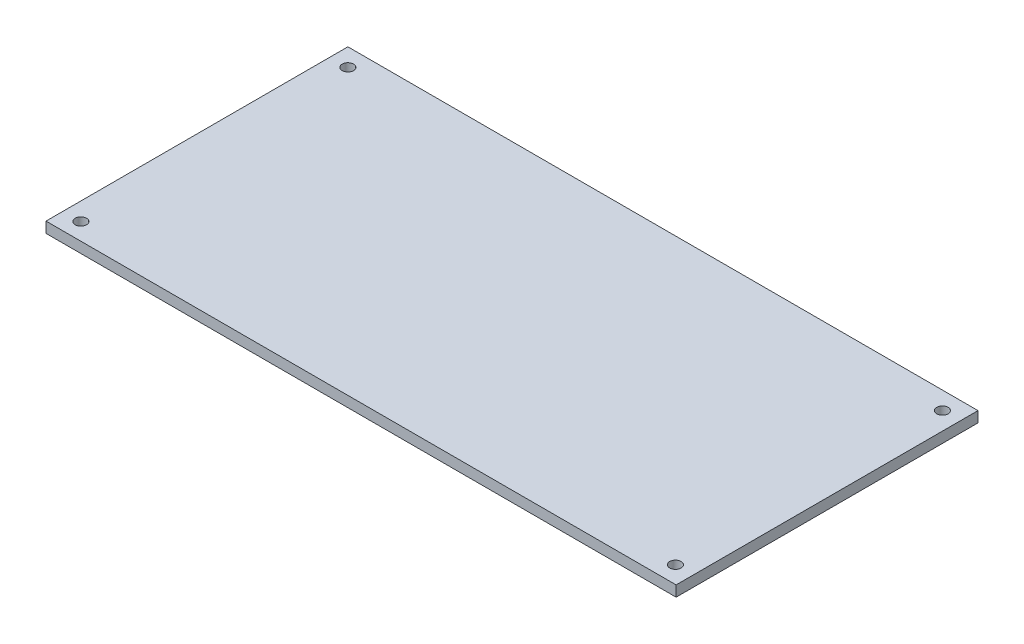
SolidWorks part; units mm, degrees
ref_plane "Front Plane" through (0, 0, 0) normal (0, 0, 1) x (1, 0, 0)
ref_plane "Top Plane" through (0, 0, 0) normal (0, 1, 0) x (1, 0, 0)
ref_plane "Right Plane" through (0, 0, 0) normal (1, 0, 0) x (0, 0, -1)
sketch "Sketch1" plane through (0, 0, 0) normal (0, 1, 0) x (1, 0, 0)
  line L1 (-88.5, -42.4) -> (88.5, -42.4)
  line L2 (-88.5, -42.4) -> (-88.5, 42.4)
  line L3 (-88.5, 42.4) -> (88.5, 42.4)
  line L4 (88.5, -42.4) -> (88.5, 42.4)
  line L5 (-88.5, -42.4) -> (88.5, 42.4) construction
  line L6 (-88.5, 42.4) -> (88.5, -42.4) construction
  point P0 (0, 0)
  dimension "D1" = 177
  dimension "D2" = 84.8
extrude "Boss-Extrude1" add sketch "Sketch1" along normal blind 3
sketch "Sketch2" plane through (0, 3, 0) normal (0, 1, 0) x (1, 0, 0)
  circle A0 centre (83.5, -37.6) radius 2.375 construction
  circle A1 centre (83.5, 37.4) radius 2.375 construction
  circle A2 centre (-83.5, 37.4) radius 2.375 construction
  circle A3 centre (-83.5, -37.6) radius 2.375 construction
  circle A4 centre (83.5, -37.6) radius 2.375 construction
  circle A5 centre (83.5, 37.4) radius 2.375 construction
  circle A6 centre (-83.5, 37.4) radius 2.375 construction
  circle A7 centre (-83.5, -37.6) radius 2.375 construction
  circle A8 centre (83.5, -37.6) radius 1.6
  circle A9 centre (83.5, 37.4) radius 1.6
  circle A10 centre (-83.5, 37.4) radius 1.6
  circle A11 centre (-83.5, -37.6) radius 1.6
  dimension "D1" = 3.2
extrude "Cut-Extrude1" cut sketch "Sketch2" against normal through all
